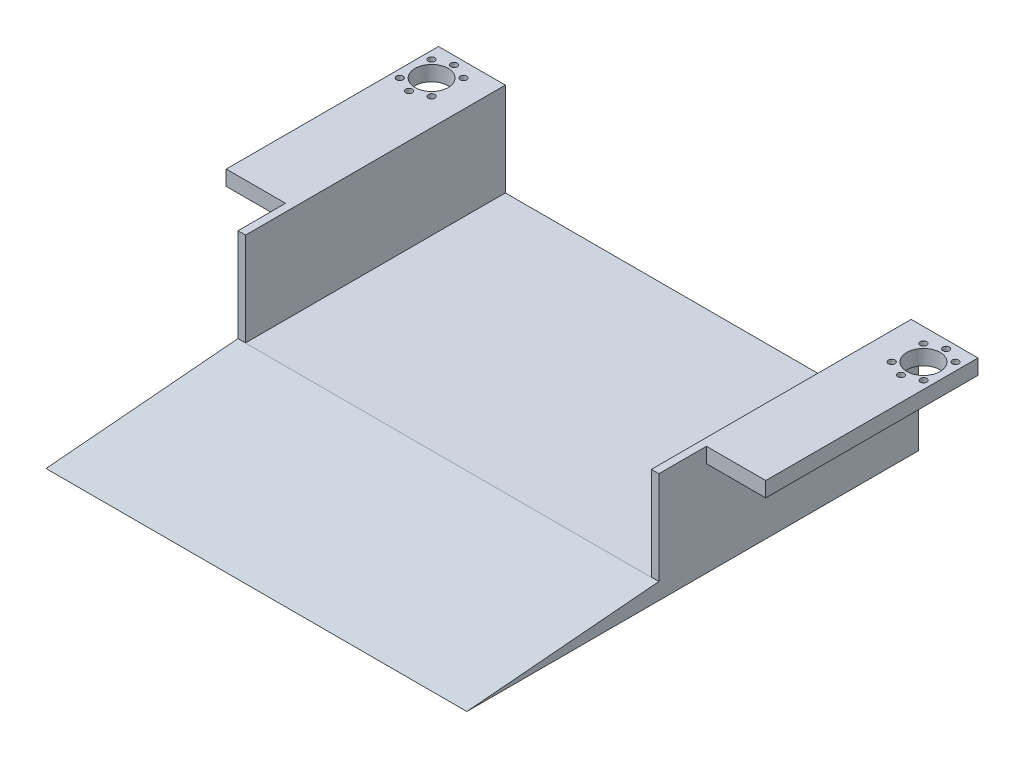
SolidWorks part; units mm, degrees
ref_plane "Front Plane" through (0, 0, 0) normal (0, 0, 1) x (1, 0, 0)
ref_plane "Top Plane" through (0, 0, 0) normal (0, 1, 0) x (1, 0, 0)
ref_plane "Right Plane" through (0, 0, 0) normal (1, 0, 0) x (0, 0, -1)
sketch "Sketch1" plane through (0, 0, 0) normal (0, 1, 0) x (1, 0, 0)
  line L1 (0, 0) -> (454.914, 0)
  line L2 (0, 0) -> (0, 381)
  line L3 (0, 381) -> (454.914, 381)
  line L4 (454.914, 0) -> (454.914, 381)
  dimension "D1" = 454.914
  dimension "D2" = 381
extrude "Boss-Extrude1" add sketch "Sketch1" along normal blind 92.6973
sketch "Sketch3" plane through (0, 92.6973, 0) normal (0, 1, 0) x (1, 0, 0)
  line L1 (454.914, 0) -> (404.9014, 0)
  line L2 (454.914, 0) -> (454.914, 202.0062)
  line L3 (454.914, 202.0062) -> (404.9014, 202.0062)
  line L4 (404.9014, 0) -> (404.9014, 202.0062)
  line L5 (0, 0) -> (50.0126, 0)
  line L6 (0, 0) -> (0, 202.0062)
  line L7 (0, 202.0062) -> (50.0126, 202.0062)
  line L8 (50.0126, 0) -> (50.0126, 202.0062)
  dimension "D1" = 202.0062
  dimension "D2" = 50.0126
  dimension "D3" = 202.0062
  dimension "D4" = 50.0126
extrude "Cut-Extrude1" cut sketch "Sketch3" against normal through all
sketch "Sketch4" plane through (0, 92.6973, 0) normal (0, 1, 0) x (1, 0, 0)
  line L0 (454.914, 381) -> (0, 381) construction
  line L1 (0, 381) -> (0, 202.0062) construction
  line L2 (454.914, 202.0062) -> (454.914, 381) construction
  circle A0 centre (20.066, 355.092) radius 14
  circle A1 centre (434.848, 355.092) radius 14
  dimension "D1" = 28
  dimension "D4" = 28
  dimension "D5" = 20.066
  dimension "D6" = 25.908
  dimension "D2" = 25.908
  dimension "D3" = 20.066
extrude "Cut-Extrude2" cut sketch "Sketch4" against normal through all
sketch "Sketch5" plane through (0, 92.6973, 0) normal (0, 1, 0) x (1, 0, 0)
  line L0 (454.914, 381) -> (0, 381) construction
  line L1 (56.3626, 381) -> (398.5514, 381)
  line L2 (56.3626, 381) -> (56.3626, 0)
  line L3 (56.3626, 0) -> (398.5514, 0)
  line L4 (398.5514, 381) -> (398.5514, 0)
  line L5 (50.0126, 0) -> (404.9014, 0) construction
  line L6 (50.0126, 0) -> (50.0126, 202.0062) construction
  line L7 (404.9014, 202.0062) -> (404.9014, 0) construction
  dimension "D1" = 6.35
  dimension "D2" = 6.35
extrude "Cut-Extrude3" cut sketch "Sketch5" against normal blind 78.74
sketch "Sketch6" plane through (454.914, 0, 0) normal (1, 0, 0) x (0, 0, -1)
  line L0 (381, 92.6973) -> (381, 0) construction
  line L1 (202.0062, 0) -> (381, 0)
  line L2 (202.0062, 0) -> (202.0062, 79.9974)
  line L3 (202.0062, 79.9974) -> (381, 79.9974)
  line L4 (381, 0) -> (381, 79.9974)
  dimension "D1" = 79.9974
extrude "Cut-Extrude4" cut sketch "Sketch6" against normal blind 50.0126
sketch "Sketch7" plane through (0, 0, 0) normal (-1, 0, 0) x (0, 0, 1)
  line L0 (-202.0062, 0) -> (-202.0062, 92.6973) construction
  line L1 (-381, 0) -> (-202.0062, 0)
  line L2 (-381, 0) -> (-381, 79.9974)
  line L3 (-381, 79.9974) -> (-202.0062, 79.9974)
  line L4 (-202.0062, 0) -> (-202.0062, 79.9974)
  dimension "D1" = 79.9974
extrude "Cut-Extrude5" cut sketch "Sketch7" against normal blind 50.0126
sketch "Sketch10" plane through (404.9014, 0, 0) normal (1, 0, 0) x (0, 0, -1)
  line L0 (0, 0) -> (161.8995, 13.97)
  line L1 (202.0062, 92.6973) -> (0, 92.6973) construction
  line L3 (161.8995, 92.6973) -> (161.8995, 13.97)
  line L8 (161.8995, 92.6973) -> (0, 92.6973)
  line L9 (0, 92.6973) -> (0, 0)
extrude "Cut-Extrude6" cut sketch "Sketch10" against normal through all
sketch "Sketch11" plane through (0, 92.6973, 0) normal (0, 1, 0) x (1, 0, 0)
  line L0 (434.848, 385.1807) -> (434.848, 325.1677) construction
  line L1 (457.9437, 355.092) -> (408.0384, 355.092) construction
  line L2 (434.848, 355.1742) -> (453.5332, 373.8594) construction
  line L3 (434.848, 355.1742) -> (419.9379, 370.0843) construction
  line L4 (434.848, 355.1742) -> (452.7645, 337.2577) construction
  line L5 (434.848, 355.1742) -> (417.2384, 337.5646) construction
  circle A1 centre (434.848, 374.1742) radius 2.75
  circle A2 centre (448.283, 368.6092) radius 2.75
  circle A3 centre (421.413, 368.6092) radius 2.75
  circle A4 centre (448.283, 341.7392) radius 2.75
  circle A5 centre (434.848, 336.1742) radius 2.75
  circle A6 centre (421.413, 341.7392) radius 2.75
  dimension "D2" = 45
  dimension "D5" = 5.5
  dimension "D6" = 5.5
  dimension "D7" = 5.5
  dimension "D8" = 5.5
  dimension "D9" = 5.5
  dimension "D10" = 5.5
  dimension "D3" = 45
  dimension "D4" = 45
extrude "Cut-Extrude7" cut sketch "Sketch11" against normal through all
sketch "Sketch12" plane through (0, 92.6973, 0) normal (0, 1, 0) x (1, 0, 0)
  line L0 (20.066, 355.092) -> (20.066, 379.9549) construction
  line L1 (20.066, 355.092) -> (42.2706, 355.092) construction
  line L2 (20.066, 355.092) -> (20.066, 337.1345) construction
  line L3 (20.066, 355.092) -> (2.8652, 355.092) construction
  line L4 (20.066, 355.092) -> (38.3107, 373.3367) construction
  line L5 (20.066, 355.092) -> (33.6036, 341.5544) construction
  line L6 (20.066, 355.092) -> (5.5449, 369.6131) construction
  line L7 (20.066, 355.092) -> (7.0967, 342.1227) construction
  circle A1 centre (20.066, 374.092) radius 2.75
  circle A2 centre (6.631, 368.527) radius 2.75
  circle A3 centre (33.501, 368.527) radius 2.75
  circle A4 centre (33.501, 341.657) radius 2.75
  circle A5 centre (20.066, 336.092) radius 2.75
  circle A6 centre (6.631, 341.657) radius 2.75
  dimension "D5" = 5.5
  dimension "D6" = 5.5
  dimension "D7" = 5.5
  dimension "D8" = 5.5
  dimension "D9" = 5.5
  dimension "D10" = 5.5
  dimension "D1" = 45
  dimension "D2" = 45
  dimension "45" = 45
  dimension "D3" = 45
extrude "Cut-Extrude8" cut sketch "Sketch12" against normal through all
